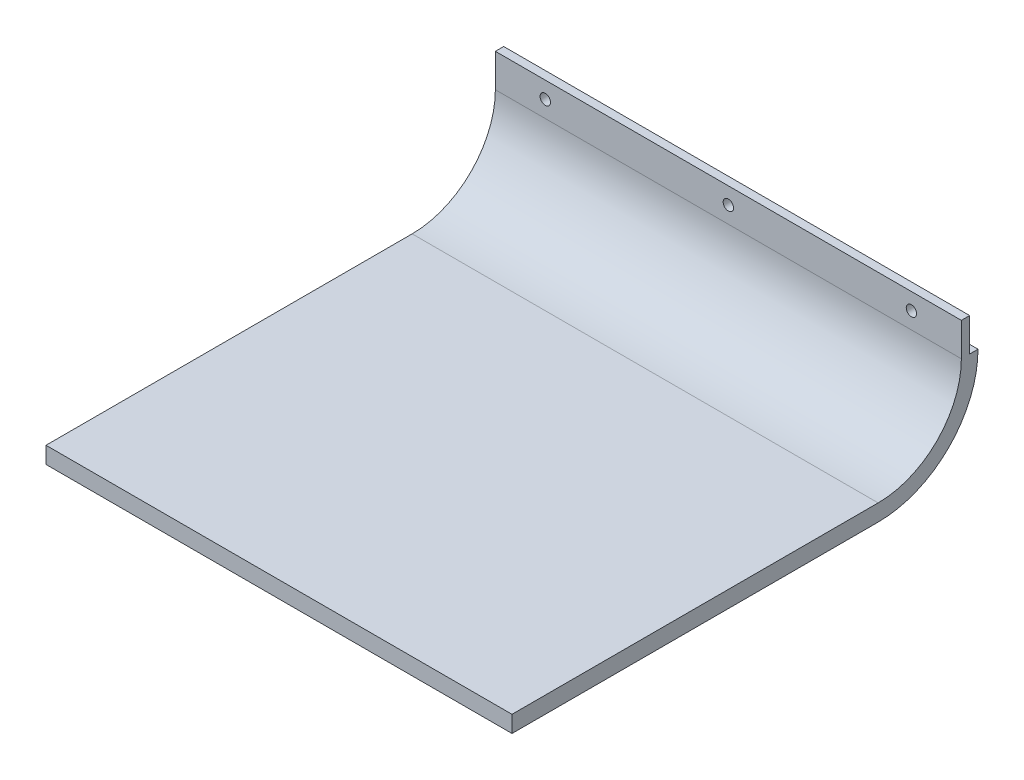
SolidWorks part; units mm, degrees
ref_plane "Front Plane" through (0, 0, 0) normal (0, 0, 1) x (1, 0, 0)
ref_plane "Top Plane" through (0, 0, 0) normal (0, 1, 0) x (1, 0, 0)
ref_plane "Right Plane" through (0, 0, 0) normal (1, 0, 0) x (0, 0, -1)
sketch "Sketch1" plane through (0, 0, 0) normal (1, 0, 0) x (0, 0, -1)
  line L0 (-139.7, 0) -> (139.7, 0)
  line L5 (139.7, 0) -> (139.7, 12.7) construction
  line L7 (-139.7, 12.7) -> (139.7, 12.7)
  line L9 (-139.7, 0) -> (-139.7, 12.7)
  line L12 (139.7, 0) -> (139.7, 152.4) construction
  line L13 (0.6365, 139.0796) -> (-139.7417, 139.9778) construction
  line L14 (-12.6991, 151.8652) -> (-139.6605, 152.6775) construction
  line L15 (203.2, 76.2) -> (215.9, 76.2)
  arc A2 (139.7, 0) -> (-12.6991, 151.8652) centre (139.7, 152.4) ccw construction
  arc A3 (139.7, 12.7) -> (0.6365, 139.0796) centre (139.7, 152.4) ccw construction
  circle A5 centre (139.7, 76.2) radius 76.2 construction
  arc A6 (215.9, 76.2) -> (139.7, 0) centre (139.7, 76.2) cw
  circle A7 centre (139.7, 76.2) radius 63.5 construction
  arc A8 (203.2, 76.2) -> (139.7, 12.7) centre (139.7, 76.2) cw
  point P3 (0, 0)
  point P17 (0, 0)
  point P18 (0, 0)
  dimension "D1" = 152.4
  dimension "D2" = 12.7
  dimension "D4" = 127
  dimension "D6" = 12.7
  dimension "D3" = 12.7
  dimension "D5" = 12.7
  dimension "D7" = 355.6
extrude "Boss-Extrude1" add sketch "Sketch1" along normal blind 177.8 and the other way blind 177.8
sketch "Sketch2" plane through (0, 76.2, 0) normal (0, 1, 0) x (1, 0, 0)
  line L0 (-177.8, 215.9) -> (-177.8, 203.2) construction
  line L1 (-177.8, 209.55) -> (177.8, 209.55)
  line L2 (-177.8, 209.55) -> (-177.8, 203.2)
  line L3 (-177.8, 203.2) -> (177.8, 203.2)
  line L4 (177.8, 209.55) -> (177.8, 203.2)
extrude "Boss-Extrude2" add sketch "Sketch2" along normal blind 25.4
sketch "Sketch3" plane through (0, 0, -209.55) normal (0, 0, -1) x (-1, 0, 0)
  line L0 (-177.8, 88.9) -> (177.8, 88.9) construction
  line L1 (-177.8, 101.6) -> (-177.8, 76.2) construction
  line L2 (177.8, 101.6) -> (177.8, 76.2) construction
  line L3 (-139.7, 101.6) -> (-139.7, 76.2) construction
  line L4 (-177.8, 101.6) -> (177.8, 101.6) construction
  line L5 (-177.8, 76.2) -> (177.8, 76.2) construction
  line L6 (0, 101.6) -> (0, 76.2) construction
  line L7 (177.8, 76.2) -> (-177.8, 76.2) construction
  line L8 (139.7, 101.6) -> (139.7, 76.2) construction
  circle A0 centre (-139.7, 88.9) radius 3.9687
  circle A1 centre (139.7, 88.9) radius 3.9687
  circle A2 centre (0, 88.9) radius 3.9687
  dimension "D3" = 7.9375
  dimension "D1" = 139.7
  dimension "D2" = 139.7
extrude "Cut-Extrude1" cut sketch "Sketch3" against normal blind 25.4
